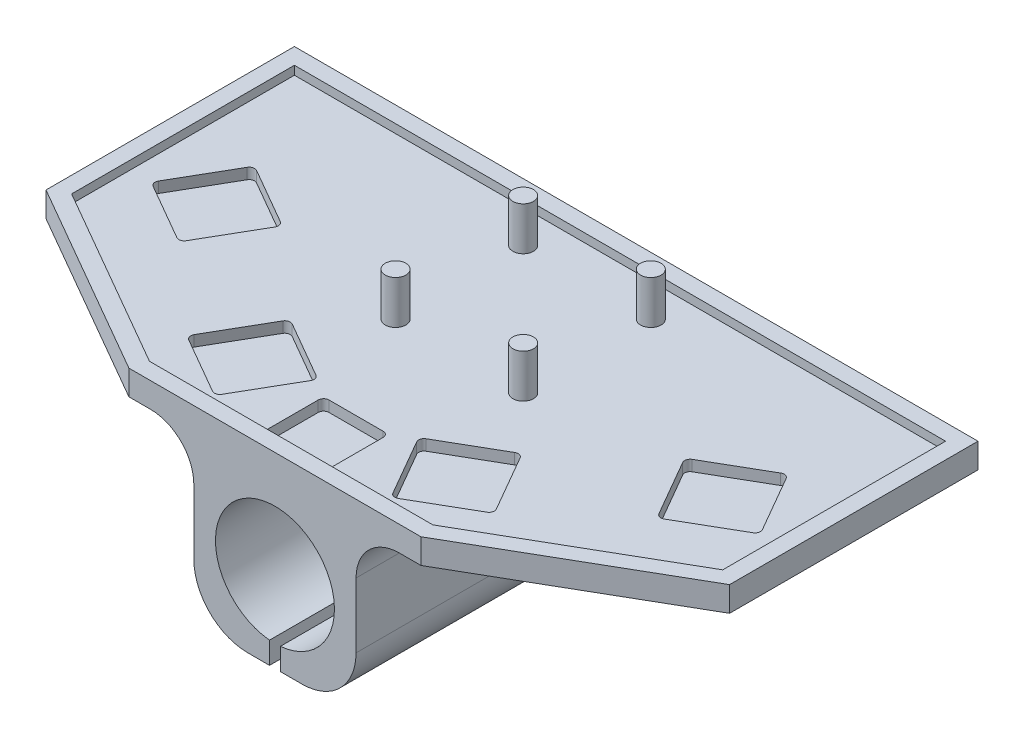
SolidWorks part; units mm, degrees
ref_plane "Спереди" through (0, 0, 0) normal (0, 0, 1) x (1, 0, 0)
ref_plane "Сверху" through (0, 0, 0) normal (0, 1, 0) x (1, 0, 0)
ref_plane "Справа" through (0, 0, 0) normal (1, 0, 0) x (0, 0, -1)
sketch "Эскиз1" plane through (0, 0, 0) normal (0, 1, 0) x (1, 0, 0)
  line L0 (60.2, 0) -> (-60.2, 0)
  line L1 (-60.2, 0) -> (-60.2, -41.2)
  line L2 (-60.2, -41.2) -> (-26.2, -60.8)
  line L3 (-26.2, -60.8) -> (26.2, -60.8)
  line L4 (26.2, -60.8) -> (60.2, -41.2)
  line L5 (60.2, -41.2) -> (60.2, 0)
  line L6 (0, 0) -> (0, -60.8) construction
  line L7 (63.2, 3) -> (-63.2, 3)
  line L8 (-63.2, 3) -> (-63.2, -42.9334)
  line L9 (-63.2, -42.9334) -> (-27.0028, -63.8)
  line L10 (-27.0028, -63.8) -> (27.0028, -63.8)
  line L11 (27.0028, -63.8) -> (63.2, -42.9334)
  line L12 (63.2, -42.9334) -> (63.2, 3)
  line L13 (-3, 0) -> (-3, -60.8)
  point P4 (0, 0)
  dimension "D1" = 120.4
  dimension "D2" = 41.2
  dimension "D3" = 60.8
  dimension "D4" = 52.4
  dimension "D5" = 3
extrude "Бобышка-Вытянуть1" add sketch "Эскиз1" along normal blind 1.6 contours L11 L12 L7 L8 L9 L10 L5 L4 L3 L2 L1 L0 region at (61.7703, 0, 19.9667)
sketch "Эскиз2" plane through (0, 0, 0) normal (0, -1, 0) x (1, 0, 0)
  line L6 (63.2, 42.9334) -> (27.0028, 63.8)
  line L7 (27.0028, 63.8) -> (-27.0028, 63.8)
  line L8 (-27.0028, 63.8) -> (-63.2, 42.9334)
  line L9 (-63.2, 42.9334) -> (-63.2, -3)
  line L10 (-63.2, -3) -> (63.2, -3)
  line L11 (63.2, -3) -> (63.2, 42.9334)
  line L12 (63.2, 42.9334) -> (27.0028, 63.8)
  line L13 (27.0028, 63.8) -> (-27.0028, 63.8)
  line L14 (-27.0028, 63.8) -> (-63.2, 42.9334)
  line L15 (-63.2, 42.9334) -> (-63.2, -3)
  line L16 (-63.2, -3) -> (63.2, -3)
  line L17 (63.2, -3) -> (63.2, 42.9334)
  dimension "D1" = 0
extrude "Бобышка-Вытянуть2" add sketch "Эскиз2" along normal blind 3
sketch "Эскиз3" plane through (0, 0, 0) normal (0, 1, 0) x (1, 0, 0)
  line L0 (-6, -60.8) -> (6, -60.8)
  line L1 (-6, -60.8) -> (-6, -48.8)
  line L2 (6, -60.8) -> (6, -48.8)
  line L3 (-6, -48.8) -> (6, -48.8)
  line L4 (-26.2, -60.8) -> (26.2, -60.8) construction
  line L5 (0, 0) -> (0, -60.8) construction
  line L6 (60.2, 0) -> (-60.2, 0) construction
  line L7 (0, -54.8) -> (60.2, -20.0435) construction
  line L8 (60.2, -41.2) -> (60.2, 0) construction
  line L9 (0, -54.8) -> (-60.2, -20.0435) construction
  line L10 (-60.2, 0) -> (-60.2, -41.2) construction
  line L11 (-6, -48.8) -> (6, -60.8) construction
  line L13 (-21.4365, -39.5369) -> (-9.3122, -46.5369)
  line L14 (-21.4365, -39.5369) -> (-28.4365, -51.6612)
  line L15 (-9.3122, -46.5369) -> (-16.3122, -58.6612)
  line L16 (-28.4365, -51.6612) -> (-16.3122, -58.6612)
  line L17 (9.3122, -46.5369) -> (21.4365, -39.5369)
  line L18 (9.3122, -46.5369) -> (16.3122, -58.6612)
  line L19 (21.4365, -39.5369) -> (28.4365, -51.6612)
  line L20 (16.3122, -58.6612) -> (28.4365, -51.6612)
  line L21 (-15.3744, -43.0369) -> (-16.6244, -45.2019) construction
  line L22 (15.3744, -43.0369) -> (16.6244, -45.2019) construction
  line L23 (56.3275, -30.3622) -> (44.2032, -37.3622)
  line L24 (56.3275, -30.3622) -> (49.3275, -18.2378)
  line L25 (44.2032, -37.3622) -> (37.2032, -25.2378)
  line L26 (49.3275, -18.2378) -> (37.2032, -25.2378)
  line L27 (56.3275, -30.3622) -> (37.2032, -25.2378) construction
  line L28 (44.2032, -37.3622) -> (49.3275, -18.2378) construction
  line L29 (-44.2032, -37.3622) -> (-37.2032, -25.2378)
  line L30 (-44.2032, -37.3622) -> (-56.3275, -30.3622)
  line L31 (-37.2032, -25.2378) -> (-49.3275, -18.2378)
  line L32 (-56.3275, -30.3622) -> (-49.3275, -18.2378)
  line L33 (-44.2032, -37.3622) -> (-49.3275, -18.2378) construction
  line L34 (-37.2032, -25.2378) -> (-56.3275, -30.3622) construction
  point P30 (46.7654, -27.8)
  point P31 (-46.7654, -27.8)
  dimension "D1" = 120
  dimension "D2" = 12
  dimension "D3" = 14
  dimension "D4" = 4
  dimension "D5" = 2.5
  dimension "D6" = 4
  dimension "D7" = 54
  dimension "D8" = 54
extrude "Вырез-Вытянуть1" cut sketch "Эскиз3" against normal blind 2
fillet "Скругление1" radius 1 20 edges at (44.2032, -1, 37.3622) (37.2032, -1, 25.2378) (49.3275, -1, 18.2378) (56.3275, -1, 30.3622) (28.4365, -1, 51.6612) (16.3122, -1, 58.6612) (9.3122, -1, 46.5369) (21.4365, -1, 39.5369) (-6, -1, 48.8) (6, -1, 48.8) (6, -1, 60.8) (-6, -1, 60.8) (-28.4365, -1, 51.6612) (-16.3122, -1, 58.6612) (-9.3122, -1, 46.5369) (-21.4365, -1, 39.5369) (-56.3275, -1, 30.3622) (-44.2032, -1, 37.3622) (-37.2032, -1, 25.2378) (-49.3275, -1, 18.2378)
sketch "Эскиз4" plane through (0, 0, 0) normal (0, 1, 0) x (1, 0, 0)
  line L0 (0, 0) -> (0, -17.9) construction
  line L1 (11.8, -6.1) -> (-11.8, -6.1) construction
  line L2 (11.8, -6.1) -> (11.8, -29.7) construction
  line L3 (11.8, -29.7) -> (-11.8, -29.7) construction
  line L4 (-11.8, -6.1) -> (-11.8, -29.7) construction
  line L5 (11.8, -6.1) -> (-11.8, -29.7) construction
  line L6 (11.8, -29.7) -> (-11.8, -6.1) construction
  line L7 (60.2, 0) -> (-60.2, 0) construction
  line L8 (60.2, 0) -> (-60.2, 0) construction
  circle A0 centre (-11.8, -6.1) radius 1.9
  circle A1 centre (-11.8, -29.7) radius 1.9
  circle A2 centre (11.8, -29.7) radius 1.9
  circle A3 centre (11.8, -6.1) radius 1.9
  point P0 (0, -17.9)
  dimension "D3" = 3.8
  dimension "D1" = 23.6
  dimension "D2" = 6.1
extrude "Бобышка-Вытянуть3" add sketch "Эскиз4" along normal blind 8
sketch "Эскиз12" plane through (0, 0, 63.8) normal (0, 0, 1) x (1, 0, 0)
  line L1 (27.0028, -3) -> (-27.0028, -3) construction
  line L2 (-5, -33) -> (5, -33)
  line L3 (-15, -23) -> (-15, -3)
  line L4 (15, -23) -> (15, -3)
  line L5 (-15, -3) -> (15, -3)
  line L6 (11, -18) -> (15, -18) construction
  line L7 (0, -29) -> (0, -33) construction
  line L8 (0, -7) -> (0, -3) construction
  circle A0 centre (0, -18) radius 11
  arc A1 (5, -33) -> (15, -23) centre (5, -23) ccw
  arc A2 (-15, -23) -> (-5, -33) centre (-5, -23) ccw
  dimension "D1" = 22
  dimension "D2" = 4
  dimension "D3" = 10
extrude "Бобышка-Вытянуть9" add sketch "Эскиз12" against normal up to surface (66.8 mm away) up to face at (0, -0.7, -3)
sketch "Эскиз13" plane through (0, 0, -3) normal (0, 0, -1) x (-1, 0, 0)
  line L0 (-1, -33) -> (1, -33)
  line L1 (-1, -33) -> (-1, -28.9545)
  line L2 (1, -33) -> (1, -28.9545)
  line L3 (-1, -28.9545) -> (1, -28.9545)
  line L4 (-5, -33) -> (5, -33) construction
  circle A0 centre (0, -18) radius 11 construction
  dimension "D1" = 2
extrude "Вырез-Вытянуть2" cut sketch "Эскиз13" against normal through all both and the other way through all
sketch "Эскиз16" plane through (-15, 0, 0) normal (-1, 0, 0) x (0, 0, 1)
  line L0 (63.8, -13) -> (-3, -13) construction
  line L1 (63.8, -3) -> (63.8, -23) construction
  line L2 (-3, -23) -> (-3, -3) construction
  line L3 (9, -3) -> (17, -3)
  line L4 (9, -3) -> (9, -5)
  line L5 (17, -3) -> (17, -5)
  line L6 (9, -5) -> (17, -5)
  line L8 (43.8, -3) -> (51.8, -3)
  line L9 (43.8, -3) -> (43.8, -5)
  line L10 (51.8, -3) -> (51.8, -5)
  line L11 (43.8, -5) -> (51.8, -5)
  line L14 (-3, -3) -> (63.8, -3) construction
  dimension "D1" = 8
  dimension "D2" = 2
  dimension "D3" = 12
  dimension "D4" = 12
extrude "Вырез-Вытянуть5" cut sketch "Эскиз16" against normal through all both and the other way through all
fillet "Скругление2" radius 8 4 edges at (15, -3, 57.8) (15, -3, 3) (-15, -3, 3) (-15, -3, 57.8)
